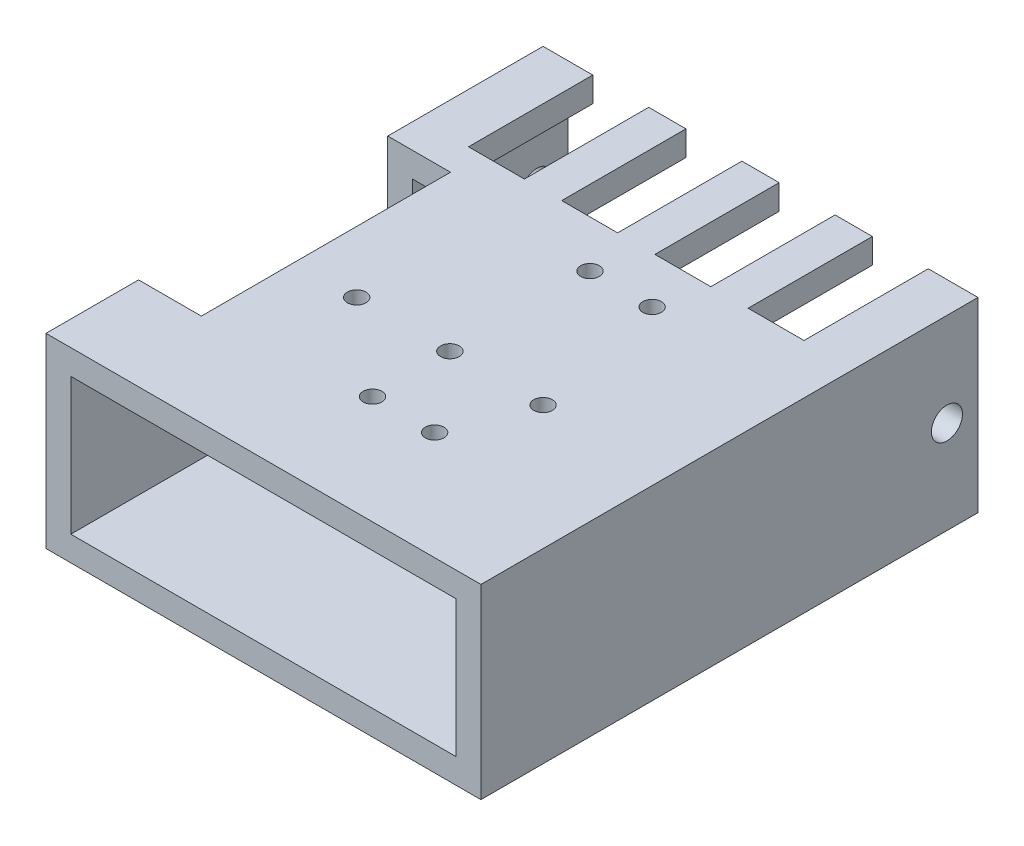
SolidWorks part; units mm, degrees
ref_plane "Front Plane" through (0, 0, 0) normal (0, 0, 1) x (1, 0, 0)
ref_plane "Top Plane" through (0, 0, 0) normal (0, 1, 0) x (1, 0, 0)
ref_plane "Right Plane" through (0, 0, 0) normal (1, 0, 0) x (0, 0, -1)
sketch "Sketch1" plane through (0, 0, 0) normal (0, 1, 0) x (1, 0, 0)
  line L1 (0, 0) -> (88.9, 0)
  line L2 (0, 0) -> (0, 101.6)
  line L3 (0, 101.6) -> (88.9, 101.6)
  line L4 (88.9, 0) -> (88.9, 101.6)
  dimension "D1" = 101.6
  dimension "D2" = 88.9
extrude "Boss-Extrude1" add sketch "Sketch1" along normal blind 38.1 contours L1 L4 L3 L2
shell "Shell1" thickness 5.08 removed face at (44.45, 19.05, -101.6) removed face at (44.45, 19.05, 0)
sketch "Sketch4" plane through (0, 0, 0) normal (0, -1, 0) x (1, 0, 0)
  line L0 (0, 0) -> (0, -101.6) construction
  line L1 (0, -18.923) -> (12.827, -18.923)
  line L2 (0, -18.923) -> (0, -69.85)
  line L3 (0, -69.85) -> (12.827, -69.85)
  line L4 (12.827, -18.923) -> (12.827, -69.85)
  line L5 (0, -101.6) -> (88.9, -101.6) construction
  dimension "D1" = 50.927
  dimension "D2" = 12.827
  dimension "D3" = 31.75
extrude "Cut-Extrude3" cut sketch "Sketch4" against normal through all from offset 19.05 offset against normal yes
sketch "Sketch5" plane through (0, 38.1, 0) normal (0, 1, 0) x (1, 0, 0)
  line L0 (0, 101.6) -> (88.9, 101.6) construction
  line L1 (10.16, 101.6) -> (21.59, 101.6)
  line L2 (10.16, 101.6) -> (10.16, 76.2)
  line L3 (10.16, 76.2) -> (21.59, 76.2)
  line L4 (21.59, 101.6) -> (21.59, 76.2)
  line L5 (29.21, 101.6) -> (29.21, 76.2)
  line L6 (29.21, 101.6) -> (40.64, 101.6)
  line L7 (40.64, 101.6) -> (40.64, 76.2)
  line L8 (29.21, 76.2) -> (40.64, 76.2)
  line L9 (48.26, 101.6) -> (48.26, 76.2)
  line L10 (48.26, 101.6) -> (59.69, 101.6)
  line L11 (59.69, 101.6) -> (59.69, 76.2)
  line L12 (48.26, 76.2) -> (59.69, 76.2)
  line L13 (67.31, 101.6) -> (67.31, 76.2)
  line L14 (67.31, 101.6) -> (78.74, 101.6)
  line L15 (78.74, 101.6) -> (78.74, 76.2)
  line L16 (67.31, 76.2) -> (78.74, 76.2)
  line L17 (10.16, 88.9) -> (78.74, 88.9) construction
  line L19 (10.16, 101.6) -> (5.08, 101.6) construction
  line L20 (0, 69.85) -> (0, 101.6) construction
  line L21 (78.74, 101.6) -> (83.82, 101.6) construction
  line L22 (88.9, 0) -> (88.9, 101.6) construction
  point P20 (15.875, 76.2)
  point P23 (34.925, 76.2)
  dimension "D1" = 25.4
  dimension "D2" = 11.43
  dimension "D4" = 5.08
  dimension "D5" = 5.08
  dimension "D6" = 19.05
  dimension "D3" = 4
extrude "Cut-Extrude4" cut sketch "Sketch5" against normal through all
sketch "Sketch6" plane through (0, 0, 0) normal (-1, 0, 0) x (0, 0, 1)
  line L0 (-101.6, 38.1) -> (-101.6, 0) construction
  circle A0 centre (-95.25, 19.05) radius 3.175
  point P6 (-101.6, 19.05)
  dimension "D1" = 6.35
  dimension "0.25" = 6.35
extrude "Cut-Extrude5" cut sketch "Sketch6" against normal through all and the other way blind 4.2672
sketch "Sketch7" plane through (0, 38.1, 0) normal (0, 1, 0) x (1, 0, 0)
  line L0 (0, 0) -> (88.9, 0) construction
  line L1 (48.26, 76.2) -> (59.69, 76.2) construction
  line L2 (25.4, 38.1) -> (63.5, 38.1) construction
  line L4 (12.827, 44.3865) -> (50.927, 44.3865) construction
  line L5 (12.827, 69.85) -> (12.827, 18.923) construction
  line L6 (50.927, 66.6115) -> (50.927, 22.1615) construction
  circle A0 centre (44.45, 38.1) radius 1.905
  circle A2 centre (25.4, 38.1) radius 1.905
  circle A3 centre (63.5, 38.1) radius 1.905
  circle A6 centre (44.577, 66.6115) radius 1.905
  circle A7 centre (57.277, 66.6115) radius 1.905
  circle A8 centre (57.277, 22.1615) radius 1.905
  circle A9 centre (44.577, 22.1615) radius 1.905
  point P4 (44.45, 0)
  point P17 (50.927, 44.3865)
  point P20 (0, 0)
  dimension "D1" = 3.81
  dimension "D6" = 3.81
  dimension "D2" = 38.1
  dimension "D3" = 19.05
  dimension "D4" = 38.1
  dimension "D5" = 44.45
  dimension "D7" = 6.35
extrude "Cut-Extrude6" cut sketch "Sketch7" against normal up to next
sketch "Sketch9" plane through (0, 0, 0) normal (-1, 0, 0) x (0, 0, 1)
  line L0 (0, 0) -> (-101.6, 0) construction
  line L1 (-59.69, 0) -> (-49.53, 0)
  line L2 (-59.69, 0) -> (-59.69, 6.35)
  line L3 (-59.69, 6.35) -> (-49.53, 6.35)
  line L4 (-49.53, 0) -> (-49.53, 6.35)
  line L5 (-44.3865, 19.05) -> (-44.3865, 0) construction
  line L6 (-18.923, 19.05) -> (-69.85, 19.05) construction
  line L7 (-69.85, 38.1) -> (-69.85, 19.05) construction
  line L8 (-29.083, 6.35) -> (-39.243, 6.35)
  line L9 (-39.243, 0) -> (-39.243, 6.35)
  line L10 (-29.083, 0) -> (-39.243, 0)
  line L11 (-29.083, 0) -> (-29.083, 6.35)
  dimension "D1" = 10.16
  dimension "D2" = 10.16
  dimension "D3" = 6.35
extrude "Boss-Extrude2" add sketch "Sketch9" along normal blind 6.35
sketch "Sketch10" plane through (0, 0, -29.083) normal (0, 0, 1) x (1, 0, 0)
  line L0 (-6.35, 0) -> (0, 0) construction
  line L3 (0, 0) -> (-6.35, 0) construction
  line L4 (-6.35, 6.35) -> (-6.35, 0) construction
  line L5 (-6.35, 6.35) -> (0, 6.35) construction
  line L8 (-3.175, 6.35) -> (-6.35, 6.35)
  line L9 (-6.35, 6.35) -> (-6.35, 0)
  line L10 (-6.35, 0) -> (-3.175, 0)
  circle A0 centre (-3.175, 3.175) radius 2.3812
  arc A1 (-3.175, 0) -> (-3.175, 6.35) centre (-3.175, 3.175) cw
  point P3 (-3.2794, 0)
  point P7 (-3.175, 6.35)
  point P13 (0, 0)
  point P14 (-3.9877, 0)
  point P17 (0, 0)
  dimension "D1" = 4.7625
extrude "Cut-Extrude8" cut sketch "Sketch10" against normal up to surface (30.607 mm away) contours A0 up to face at (-3.175, 3.175, -59.69)
sketch "Sketch11" plane through (0, 0, -29.083) normal (0, 0, 1) x (1, 0, 0)
  line L0 (-6.35, 6.35) -> (0, 6.35) construction
  line L1 (-6.35, 0) -> (0, 0) construction
  line L2 (-6.35, 0) -> (-6.35, 6.35) construction
  line L7 (-3.175, 7.6651) -> (-3.175, 6.35)
  line L8 (-3.175, -1.3151) -> (-3.175, 0)
  arc A0 (-3.175, 6.35) -> (-3.175, 0) centre (-3.175, 3.175) ccw
  arc A1 (-3.175, 7.6651) -> (-3.175, -1.3151) centre (-3.175, 3.175) ccw
extrude "Cut-Extrude9" cut sketch "Sketch11" against normal up to surface (30.607 mm away) up to face at (-0.7938, 3.175, -59.69)
